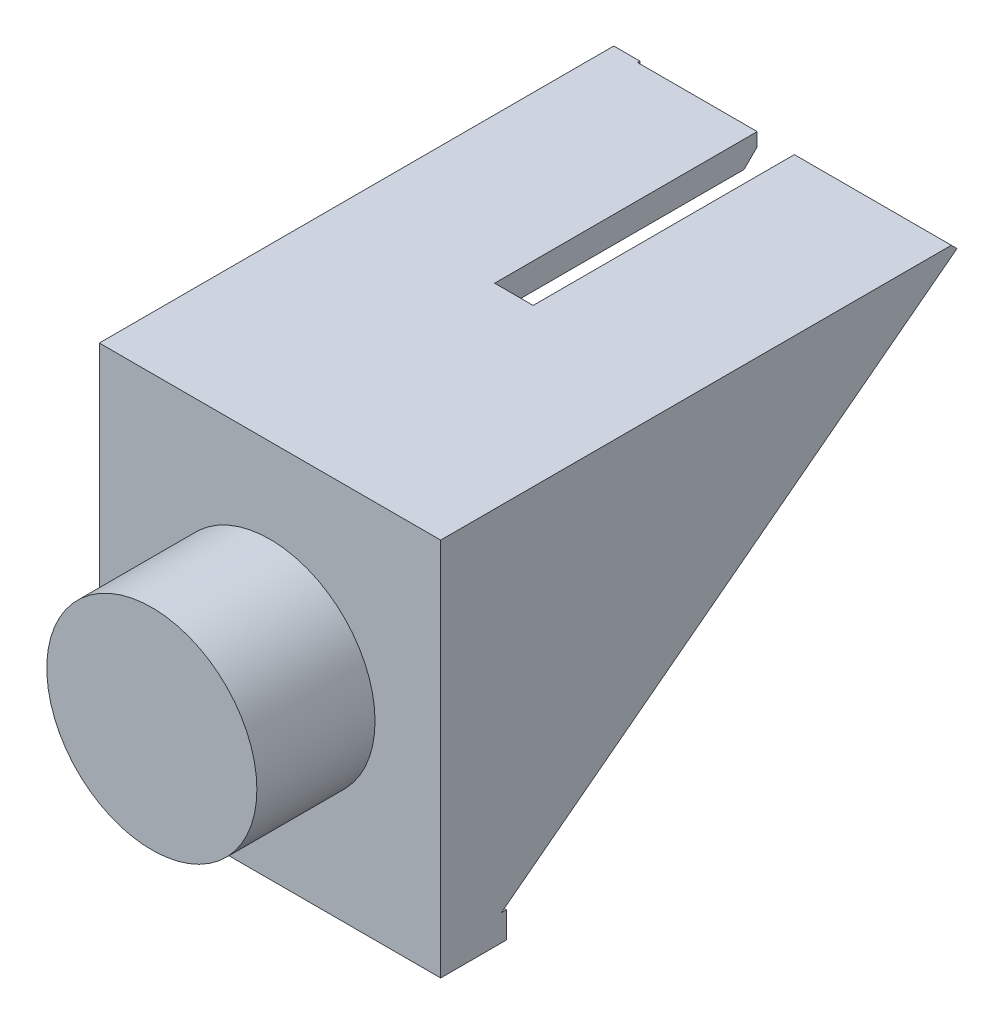
SolidWorks part; units mm, degrees
ref_plane "Alzado" through (0, 0, 0) normal (0, 0, 1) x (1, 0, 0)
ref_plane "Planta" through (0, 0, 0) normal (0, 1, 0) x (1, 0, 0)
ref_plane "Vista lateral" through (0, 0, 0) normal (1, 0, 0) x (0, 0, -1)
sketch "Croquis1" plane through (0, 0, 0) normal (0, 0, 1) x (1, 0, 0)
  line L30 (-2, 23.6) -> (-2, 20.4)
  line L31 (-2, 20.4) -> (-2, -5.2848)
  line L32 (-2, -5.2848) -> (24, -5.2848)
  line L33 (24, -5.2848) -> (24, 20.4)
  line L34 (24, 20.4) -> (24, 23.6)
  line L35 (24, 23.6) -> (-2, 23.6)
  line L36 (-2, 23.6) -> (-2, 20.4)
  line L37 (-2, 20.4) -> (-2, -5.2848)
  line L38 (-2, -5.2848) -> (24, -5.2848)
  line L39 (24, -5.2848) -> (24, 20.4)
  line L40 (24, 20.4) -> (24, 23.6)
  line L41 (24, 23.6) -> (-2, 23.6)
  dimension "D1" = 2
extrude "Saliente-Extruir1" add sketch "Croquis1" along normal blind 2
sketch "Croquis2" plane through (24, 0, 0) normal (1, 0, 0) x (0, 0, -1)
  line L0 (0, 23.6) -> (37.896, 23.6)
  line L1 (37.896, 23.6) -> (0, -5.2848)
  line L2 (0, -5.2848) -> (0, 23.6)
extrude "Saliente-Extruir2" add sketch "Croquis2" against normal blind 2
sketch "Croquis4" plane through (-2, 0, 0) normal (-1, 0, 0) x (0, 0, 1)
  line L0 (-37.896, 23.6) -> (0, 23.6)
  line L1 (0, 23.6) -> (0, -5.2848)
  line L2 (0, -5.2848) -> (-9.5342, 1.9823)
  line L3 (-13.454, 19.3047) -> (-32.2607, 19.3047)
  line L4 (-32.2607, 19.3047) -> (-37.896, 23.6)
  arc A0 (-9.5342, 1.9823) -> (-13.454, 19.3047) centre (-13.454, 10.2) ccw
extrude "Saliente-Extruir3" add sketch "Croquis4" against normal blind 2
sketch "Croquis5" plane through (0, 0, 0) normal (0, 0, -1) x (-1, 0, 0)
  line L1 (0, 23.6) -> (-22, 23.6)
  line L2 (0, 23.6) -> (0, 21.6)
  line L3 (0, 21.6) -> (-22, 21.6)
  line L4 (-22, 23.6) -> (-22, 21.6)
extrude "Saliente-Extruir4" add sketch "Croquis5" along normal blind 17
sketch "Croquis6" plane through (0, 0, 0) normal (0, 0, -1) x (-1, 0, 0)
  line L11 (-0.1421, -3.2848) -> (2, -3.2848) construction
  line L12 (-22, -3.2848) -> (0, -3.2848) construction
  line L13 (2, 1.9823) -> (2, -5.2848) construction
  line L15 (-24, -5.2848) -> (2, -5.2848)
  line L16 (-24, -5.2848) -> (-24, -3.2848)
  line L17 (-24, -3.2848) -> (2, -3.2848)
  line L18 (2, -5.2848) -> (2, -3.2848)
extrude "Saliente-Extruir5" add sketch "Croquis6" along normal blind 3
sketch "Croquis7" plane through (0, 0, -17) normal (0, 0, -1) x (-1, 0, 0)
  line L0 (-11, 23.6) -> (-11, -5.2848) construction
  line L4 (0, 23.6) -> (-9.1092, 23.6)
  line L5 (0, 23.6) -> (0, 21.6)
  line L7 (0, 21.6) -> (-9.1092, 21.6)
  line L8 (-9.1092, 23.6) -> (-9.1092, 21.6)
  line L10 (-22, 23.6) -> (-12.0412, 23.6)
  line L11 (-22, 23.6) -> (-22, 21.6)
  line L12 (-22, 21.6) -> (-12.0412, 21.6)
  line L13 (-12.0412, 23.6) -> (-12.0412, 21.6)
extrude "Saliente-Extruir6" add sketch "Croquis7" along normal blind 20
chamfer "Chaflán1" distance 1 angle 45 2 edges at (4.5546, 21.6, -37) (17.0206, 21.6, -37)
chamfer "Chaflán2" distance 1 angle 45 2 edges at (23, 23.6, -37.896) (-1, 23.6, -37.896)
sketch "Croquis8" plane through (0, 0, 2) normal (0, 0, 1) x (1, 0, 0)
  line L0 (-2, 23.6) -> (24, -5.2848) construction
  circle A0 centre (11, 9.1576) radius 8
extrude "Saliente-Extruir7" add sketch "Croquis8" along normal blind 9
